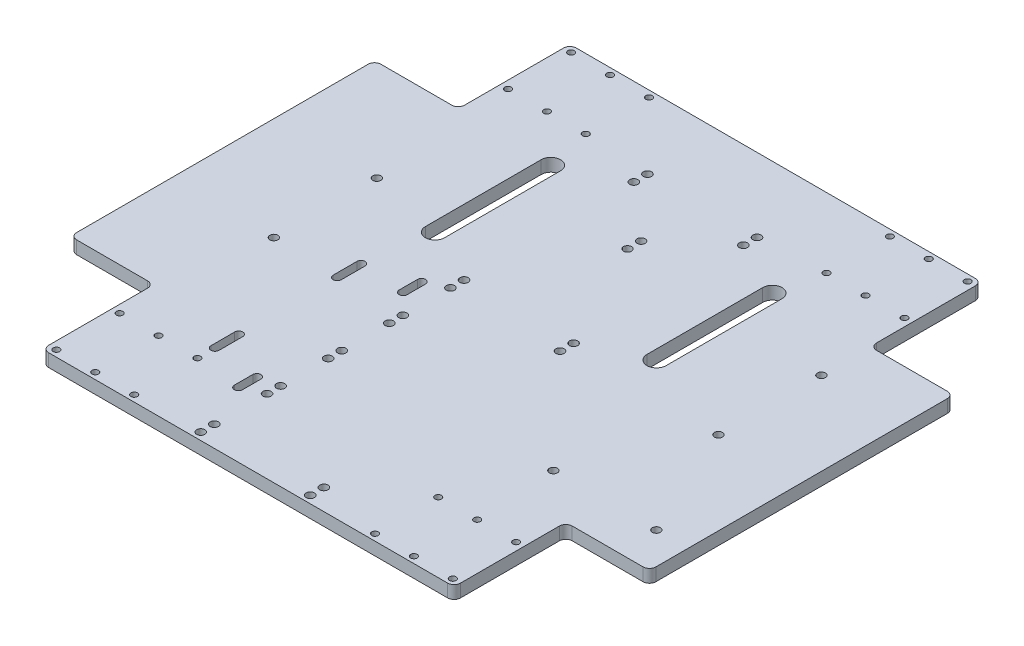
SolidWorks part; units mm, degrees
ref_plane "Front Plane" through (0, 0, 0) normal (0, 0, 1) x (1, 0, 0)
ref_plane "Top Plane" through (0, 0, 0) normal (0, 1, 0) x (1, 0, 0)
ref_plane "Right Plane" through (0, 0, 0) normal (1, 0, 0) x (0, 0, -1)
sketch "Sketch1" plane through (0, 0, 0) normal (0, 1, 0) x (1, 0, 0)
  line L1 (-101.6, 130.175) -> (101.6, 130.175)
  line L2 (-101.6, 130.175) -> (-101.6, -130.175)
  line L3 (-101.6, -130.175) -> (101.6, -130.175)
  line L4 (101.6, 130.175) -> (101.6, -130.175)
  line L5 (-101.6, 130.175) -> (101.6, -130.175) construction
  line L6 (-101.6, -130.175) -> (101.6, 130.175) construction
  point P0 (0, 0)
  dimension "D1" = 260.35
  dimension "D2" = 203.2
extrude "Boss-Extrude1" add sketch "Sketch1" against normal blind 6.35
sketch "Sketch2" plane through (0, 0, 0) normal (0, 1, 0) x (1, 0, 0)
  line L0 (0, 130.175) -> (0, -130.175) construction
  line L1 (101.6, 0) -> (-101.6, 0) construction
  line L2 (-27.0205, -117.2972) -> (27.0205, -117.2972)
  line L3 (-27.0205, -117.2972) -> (-27.0205, -124.0028)
  line L4 (101.6, -130.175) -> (101.6, 130.175)
  line L5 (101.6, 130.175) -> (-101.6, 130.175)
  line L6 (-101.6, 130.175) -> (-101.6, -130.175)
  line L7 (-101.6, -130.175) -> (101.6, -130.175)
  line L8 (101.6, -130.175) -> (101.6, 130.175)
  line L9 (101.6, 130.175) -> (-101.6, 130.175)
  line L10 (-101.6, 130.175) -> (-101.6, -130.175)
  line L11 (-101.6, -130.175) -> (101.6, -130.175)
  line L12 (-27.0205, -124.0028) -> (27.0205, -124.0028)
  line L13 (27.0205, -117.2972) -> (27.0205, -124.0028)
  line L14 (-27.0205, -117.2972) -> (27.0205, -124.0028) construction
  line L15 (-27.0205, -124.0028) -> (27.0205, -117.2972) construction
  line L16 (-27.0205, -87.1347) -> (-27.0205, -93.8403)
  line L17 (-27.0205, -87.1347) -> (27.0205, -87.1347)
  line L18 (27.0205, -87.1347) -> (27.0205, -93.8403)
  line L19 (-27.0205, -93.8403) -> (27.0205, -93.8403)
  line L20 (-27.0205, -56.9722) -> (-27.0205, -63.6778)
  line L21 (-27.0205, -56.9722) -> (27.0205, -56.9722)
  line L22 (27.0205, -56.9722) -> (27.0205, -63.6778)
  line L23 (-27.0205, -63.6778) -> (27.0205, -63.6778)
  line L24 (-27.0205, -26.8097) -> (-27.0205, -33.5153)
  line L25 (-27.0205, -26.8097) -> (27.0205, -26.8097)
  line L26 (27.0205, -26.8097) -> (27.0205, -33.5153)
  line L27 (-27.0205, -33.5153) -> (27.0205, -33.5153)
  line L28 (-27.0205, 3.3528) -> (-27.0205, -3.3528)
  line L29 (-27.0205, 3.3528) -> (27.0205, 3.3528)
  line L30 (27.0205, 3.3528) -> (27.0205, -3.3528)
  line L31 (-27.0205, -3.3528) -> (27.0205, -3.3528)
  line L32 (-27.0205, 33.5153) -> (-27.0205, 26.8097)
  line L33 (-27.0205, 33.5153) -> (27.0205, 33.5153)
  line L34 (27.0205, 33.5153) -> (27.0205, 26.8097)
  line L35 (-27.0205, 26.8097) -> (27.0205, 26.8097)
  line L36 (-27.0205, 63.6778) -> (-27.0205, 56.9722)
  line L37 (-27.0205, 63.6778) -> (27.0205, 63.6778)
  line L38 (27.0205, 63.6778) -> (27.0205, 56.9722)
  line L39 (-27.0205, 56.9722) -> (27.0205, 56.9722)
  line L40 (-27.0205, 93.8403) -> (-27.0205, 87.1347)
  line L41 (-27.0205, 93.8403) -> (27.0205, 93.8403)
  line L42 (27.0205, 93.8403) -> (27.0205, 87.1347)
  line L43 (-27.0205, 87.1347) -> (27.0205, 87.1347)
  line L44 (-27.0205, 124.0028) -> (-27.0205, 117.2972)
  line L45 (-27.0205, 124.0028) -> (27.0205, 124.0028)
  line L46 (27.0205, 124.0028) -> (27.0205, 117.2972)
  line L47 (-27.0205, 117.2972) -> (27.0205, 117.2972)
  line L48 (-27.0205, -124.0028) -> (-27.0205, -126.5428)
  line L49 (-27.0205, -117.2972) -> (-27.0205, -119.8372)
  circle A0 centre (-27.0205, -117.2972) radius 2.032
  circle A1 centre (-27.0205, -124.0028) radius 2.032
  circle A2 centre (27.0205, -124.0028) radius 2.032
  circle A3 centre (27.0205, -117.2972) radius 2.032
  circle A4 centre (-27.0205, -87.1347) radius 2.032
  circle A5 centre (-27.0205, -93.8403) radius 2.032
  circle A6 centre (27.0205, -87.1347) radius 2.032
  circle A7 centre (27.0205, -93.8403) radius 2.032
  circle A8 centre (-27.0205, -56.9722) radius 2.032
  circle A9 centre (-27.0205, -63.6778) radius 2.032
  circle A10 centre (27.0205, -56.9722) radius 2.032
  circle A11 centre (27.0205, -63.6778) radius 2.032
  circle A12 centre (-27.0205, -26.8097) radius 2.032
  circle A13 centre (-27.0205, -33.5153) radius 2.032
  circle A14 centre (27.0205, -26.8097) radius 2.032
  circle A15 centre (27.0205, -33.5153) radius 2.032
  circle A16 centre (-27.0205, 3.3528) radius 2.032
  circle A17 centre (-27.0205, -3.3528) radius 2.032
  circle A18 centre (27.0205, 3.3528) radius 2.032
  circle A19 centre (27.0205, -3.3528) radius 2.032
  circle A20 centre (-27.0205, 33.5153) radius 2.032
  circle A21 centre (-27.0205, 26.8097) radius 2.032
  circle A22 centre (27.0205, 33.5153) radius 2.032
  circle A23 centre (27.0205, 26.8097) radius 2.032
  circle A24 centre (-27.0205, 63.6778) radius 2.032
  circle A25 centre (-27.0205, 56.9722) radius 2.032
  circle A26 centre (27.0205, 63.6778) radius 2.032
  circle A27 centre (27.0205, 56.9722) radius 2.032
  circle A28 centre (-27.0205, 93.8403) radius 2.032
  circle A29 centre (-27.0205, 87.1347) radius 2.032
  circle A30 centre (27.0205, 93.8403) radius 2.032
  circle A31 centre (27.0205, 87.1347) radius 2.032
  circle A32 centre (-27.0205, 124.0028) radius 2.032
  circle A33 centre (-27.0205, 117.2972) radius 2.032
  circle A34 centre (27.0205, 124.0028) radius 2.032
  circle A35 centre (27.0205, 117.2972) radius 2.032
  circle A36 centre (-27.0205, -119.8372) radius 2.032
  circle A37 centre (-27.0205, -126.5428) radius 2.032
  circle A38 centre (27.0205, -126.5428) radius 2.032
  circle A39 centre (27.0205, -119.8372) radius 2.032
  circle A40 centre (0, 63.6778) radius 1.9939
  circle A41 centre (0, 56.9722) radius 1.9939
  point P6 (0, -120.65)
  dimension "D5" = 4.064
  dimension "D6" = 4.064
  dimension "D7" = 4.064
  dimension "D8" = 4.064
  dimension "D13" = 4.064
  dimension "D14" = 4.064
  dimension "D15" = 3.9878
  dimension "D16" = 3.9878
  dimension "D2" = 6.7056
  dimension "D3" = 54.041
  dimension "D4" = 6.1722
  dimension "D10" = 30.1625
  dimension "D11" = 2.54
  dimension "D12" = 2.54
  dimension "D1" = 0
  dimension "D9" = 9
extrude "Cut-Extrude1" cut sketch "Sketch2" against normal through all contours L43 A29 L40 | L40 A29 L43 | L41 A30 L42 | L28 A16 L29 | L29 A16 L28 | L31 A17 L28 | L28 A17 L31 | L29 A18 L30 | L30 A18 L29 | L30 A19 L31 | L31 A19 L30 | L42 A30 L41 | L43 A31 L42 | L42 A31 L43 | L41 A28 L40 | L40 A28 L41 | L25 A12 L24 | L24 A12 L25 | L27 A13 L24 | L24 A13 L27 | L21 A8 L20 | L20 A8 L21 | L20 A9 L23 | L23 A9 L20 | L17 A4 L16 | L16 A4 L17 | L16 A5 L19 | L19 A5 L16 | A36 | A37 | A39 | A38 | A40 | A41 region at (-26.1581, 0, 87.9971) region at (-27.308, 0, 86.8472) region at (-26.1581, 0, 92.9779) region at (-27.308, 0, 94.1278) region at (-26.1581, 0, 57.8346) region at (-27.308, 0, 56.6847) region at (-26.1581, 0, 62.8154) region at (-27.308, 0, 63.9653) region at (-26.1581, 0, 27.6721) region at (-27.308, 0, 26.5222) region at (-26.1581, 0, 32.6529) region at (-27.308, 0, 33.8028) region at (-26.1581, 0, -2.4904) region at (-27.308, 0, -3.6403) region at (-26.1581, 0, 2.4904) region at (-27.308, 0, 3.6403) region at (27.308, 0, -3.6403) region at (26.1581, 0, -2.4904) region at (26.1581, 0, 2.4904) region at (27.308, 0, 3.6403) region at (-26.1581, 0, -92.9779) region at (-27.308, 0, -94.1278) region at (-26.1581, 0, -87.9971) region at (-27.308, 0, -86.8472) region at (27.308, 0, -94.1278) region at (26.1581, 0, -92.9779) region at (26.1581, 0, -87.9971) region at (27.308, 0, -86.8472)
sketch "Sketch3" plane through (0, 0, 0) normal (0, 1, 0) x (1, 0, 0)
  line L0 (101.6, 130.175) -> (-101.6, 130.175) construction
  line L1 (101.6, -130.175) -> (101.6, 130.175) construction
  line L2 (-101.6, 130.175) -> (-101.6, -130.175) construction
  line L3 (-101.6, -130.175) -> (101.6, -130.175) construction
  line L4 (101.6, 130.175) -> (-101.6, 130.175)
  line L5 (101.6, -130.175) -> (101.6, 130.175)
  line L6 (-101.6, 130.175) -> (-101.6, -130.175)
  line L7 (-101.6, -130.175) -> (101.6, -130.175)
  line L8 (0, -130.175) -> (0, 130.175) construction
  line L9 (-101.6, 0) -> (101.6, 0) construction
  circle A10 centre (-85.0055, -95.8) radius 1.6
  circle A11 centre (-85.0055, -127) radius 1.6
  circle A12 centre (-78.6055, -95.8) radius 1.6
  circle A13 centre (-78.6055, -127) radius 1.6
  circle A14 centre (-72.2055, -95.8) radius 1.6
  circle A15 centre (-72.2055, -127) radius 1.6
  circle A16 centre (-65.8055, -95.8) radius 1.6
  circle A17 centre (-59.4055, -95.8) radius 1.6
  circle A18 centre (-65.8055, -127) radius 1.6
  circle A19 centre (-59.4055, -127) radius 1.6
  circle A22 centre (85.0055, -127) radius 1.6
  circle A23 centre (78.6055, -127) radius 1.6
  circle A24 centre (72.2055, -127) radius 1.6
  circle A25 centre (65.8055, -127) radius 1.6
  circle A26 centre (59.4055, -127) radius 1.6
  circle A27 centre (59.4055, -95.8) radius 1.6
  circle A28 centre (65.8055, -95.8) radius 1.6
  circle A29 centre (72.2055, -95.8) radius 1.6
  circle A30 centre (78.6055, -95.8) radius 1.6
  circle A31 centre (85.0055, -95.8) radius 1.6
  circle A32 centre (85.0055, 127) radius 1.6
  circle A33 centre (78.6055, 127) radius 1.6
  circle A34 centre (72.2055, 127) radius 1.6
  circle A35 centre (65.8055, 127) radius 1.6
  circle A36 centre (59.4055, 127) radius 1.6
  circle A37 centre (85.0055, 95.8) radius 1.6
  circle A38 centre (78.6055, 95.8) radius 1.6
  circle A39 centre (72.2055, 95.8) radius 1.6
  circle A40 centre (65.8055, 95.8) radius 1.6
  circle A41 centre (59.4055, 95.8) radius 1.6
  circle A42 centre (-59.4055, 127) radius 1.6
  circle A43 centre (-65.8055, 127) radius 1.6
  circle A44 centre (-72.2055, 127) radius 1.6
  circle A45 centre (-78.6055, 127) radius 1.6
  circle A46 centre (-85.0055, 127) radius 1.6
  circle A47 centre (-59.4055, 95.8) radius 1.6
  circle A48 centre (-65.8055, 95.8) radius 1.6
  circle A49 centre (-72.2055, 95.8) radius 1.6
  circle A50 centre (-78.6055, 95.8) radius 1.6
  circle A51 centre (-85.0055, 95.8) radius 1.6
  circle A52 centre (-91.4063, -127) radius 1.6
  circle A53 centre (-91.4063, -95.8) radius 1.6
  circle A54 centre (-97.8071, -127) radius 1.6
  circle A55 centre (-97.8071, -95.8) radius 1.6
  circle A56 centre (97.8071, -127) radius 1.6
  circle A57 centre (91.4063, -127) radius 1.6
  circle A58 centre (97.8071, -95.8) radius 1.6
  circle A59 centre (91.4063, -95.8) radius 1.6
  circle A60 centre (97.8071, 95.8) radius 1.6
  circle A61 centre (97.8071, 127) radius 1.6
  circle A62 centre (91.4063, 127) radius 1.6
  circle A63 centre (91.4063, 95.8) radius 1.6
  circle A64 centre (-97.8071, 127) radius 1.6
  circle A65 centre (-91.4063, 127) radius 1.6
  circle A66 centre (-97.8071, 95.8) radius 1.6
  circle A67 centre (-91.4063, 95.8) radius 1.6
  circle A68 centre (-27.0205, -126.5428) radius 2.032 construction
  point P9 (85.0055, -95.8)
  point P10 (78.6055, -95.8)
  point P11 (72.2055, -95.8)
  point P12 (65.8055, -95.8)
  point P13 (59.4055, -95.8)
  point P14 (78.6055, -127)
  point P15 (72.2055, -127)
  point P18 (85.0055, -127)
  point P19 (59.4055, -127)
  point P62 (85.0055, 127)
  point P65 (78.6055, 127)
  point P68 (72.2055, 127)
  point P73 (59.4055, 127)
  point P76 (85.0055, 95.8)
  point P79 (78.6055, 95.8)
  point P82 (72.2055, 95.8)
  point P85 (65.8055, 95.8)
  point P88 (59.4055, 95.8)
  dimension "D3" = 31.2
  dimension "D5" = 31.2
  dimension "D7" = 3
  dimension "D8" = 6.4008
  dimension "D9" = 32.385
  dimension "D24" = 3.2
  dimension "D25" = 3.2
  dimension "D26" = 3.2
  dimension "D27" = 3.2
  dimension "D28" = 3.2
  dimension "D31" = 3.2
  dimension "D32" = 3.2
  dimension "D33" = 3.2
  dimension "D34" = 3.2
  dimension "D35" = 3.2
  dimension "D4" = 31.2
  dimension "D6" = 31.2
  dimension "D10" = 6.4
  dimension "D11" = 6.4
  dimension "D12" = 6.4
  dimension "D13" = 6.4
  dimension "D16" = 6.4
  dimension "D17" = 6.4
  dimension "D18" = 6.4
  dimension "D19" = 6.4
  dimension "D22" = 31.2
  dimension "D37" = 3.175
extrude "Cut-Extrude2" cut sketch "Sketch3" against normal up to surface (6.35 mm away) contours A17 | A12 | A19 | A13 | A26 | A27 | A30 | A23 | A38 | A36 | A33 | A41 | A47 | A50 | A42 | A45 | A55 | A54 | A56 | A58 | A60 | A61 | A64 | A66 | A41 region at (-78.6055, 0, 95.8) region at (-78.6055, 0, 127) region at (-59.4055, 0, 95.8) region at (-59.4055, 0, 127) region at (78.6055, 0, 127) region at (59.4055, 0, 127) region at (59.4055, 0, 95.8) region at (78.6055, 0, 95.8) region at (78.6055, 0, -127) region at (59.4055, 0, -127) region at (78.6055, 0, -95.8) region at (59.4055, 0, -95.8) region at (-59.4055, 0, -127) region at (-78.6055, 0, -127) region at (-59.4055, 0, -95.8) region at (-78.6055, 0, -95.8) region at (-97.8071, 0, 127) region at (-97.8071, 0, 95.8) region at (97.8071, 0, 127) region at (97.8071, 0, 95.8) region at (97.8071, 0, -95.8) region at (97.8071, 0, -127) region at (-97.8071, 0, -127) region at (-97.8071, 0, -95.8) up to face at (-27.0205, -6.35, 28.8417)
sketch "Sketch4" plane through (0, 0, 0) normal (0, 1, 0) x (1, 0, 0)
  line L0 (-27.0205, -87.1347) -> (-27.0205, -63.6778)
  line L1 (-27.0205, -75.4063) -> (-59.4055, -75.4063)
  line L2 (-59.4055, -95.8) -> (-59.4055, -75.4063)
  line L3 (-27.0205, -87.1347) -> (-59.4055, -87.1347)
  line L4 (-61.3994, -75.4063) -> (-61.3994, -87.1347)
  line L5 (-57.4116, -75.4063) -> (-57.4116, -87.1347)
  line L6 (-27.0205, -87.1347) -> (-27.0205, -93.8403)
  line L7 (-27.0205, -90.4875) -> (-36.7792, -90.4875)
  line L8 (-36.7792, -90.4875) -> (-36.7792, -9.217)
  line L9 (-27.0205, -3.3528) -> (-27.0205, -26.8097)
  line L10 (-27.0205, -15.0813) -> (-36.7792, -15.0813)
  line L11 (-27.0205, -3.3528) -> (-36.7792, -3.3528)
  line L12 (-36.7792, -3.3528) -> (-36.7792, -15.0813)
  line L13 (-38.7731, -89.1286) -> (-38.7731, -91.8464)
  line L14 (-34.7853, -89.1286) -> (-34.7853, -91.8464)
  line L15 (-34.7853, -7.8581) -> (-34.7853, -10.5759)
  line L16 (-38.7731, -7.8581) -> (-38.7731, -10.5759)
  line L17 (-27.0205, -26.8097) -> (-59.4055, -26.8097)
  line L18 (-36.7792, -15.0813) -> (-59.4055, -15.0813)
  line L19 (-61.3994, -26.8097) -> (-61.3994, -15.0813)
  line L20 (-57.4116, -15.0813) -> (-57.4116, -26.8097)
  line L21 (-38.7731, -91.8464) -> (-38.7731, -98.1964)
  line L22 (-34.7853, -91.8464) -> (-34.7853, -98.1964)
  line L23 (-38.7731, -10.5759) -> (-38.7731, -16.9259)
  line L24 (-34.7853, -10.5759) -> (-34.7853, -16.9259)
  circle A0 centre (-27.0205, -93.8403) radius 2.032 construction
  circle A1 centre (-27.0205, -63.6778) radius 2.032 construction
  circle A2 centre (-27.0205, -87.1347) radius 2.032 construction
  circle A3 centre (-59.4055, -127) radius 1.6 construction
  circle A4 centre (-59.4055, -95.8) radius 1.6 construction
  circle A5 centre (-27.0205, -93.8403) radius 2.032
  circle A6 centre (-27.0205, -63.6778) radius 2.032
  circle A7 centre (-27.0205, -87.1347) radius 2.032
  circle A8 centre (-59.4055, -127) radius 1.6
  circle A9 centre (-59.4055, -95.8) radius 1.6
  circle A10 centre (-59.4055, -87.1347) radius 1.9939
  circle A11 centre (-59.4055, -75.4063) radius 1.9939
  circle A12 centre (-36.7792, -9.217) radius 1.9939
  circle A13 centre (-36.7792, -90.4875) radius 1.9939
  circle A16 centre (-27.0205, -3.3528) radius 2.032 construction
  circle A17 centre (-27.0205, -26.8097) radius 2.032 construction
  circle A18 centre (-27.0205, -3.3528) radius 2.032
  circle A19 centre (-27.0205, -26.8097) radius 2.032
  circle A20 centre (-36.7792, -89.1286) radius 1.9939
  circle A21 centre (-36.7792, -91.8464) radius 1.9939
  circle A22 centre (-36.7792, -7.8581) radius 1.9939
  circle A23 centre (-36.7792, -10.5759) radius 1.9939
  circle A24 centre (-59.4055, -15.0813) radius 1.9939
  circle A25 centre (-59.4055, -26.8097) radius 1.9939
  circle A26 centre (-36.7792, -98.1964) radius 1.9939
  circle A27 centre (-36.7792, -16.9259) radius 1.9939
  point P48 (-34.7853, -9.217)
  dimension "D1" = 3.9878
  dimension "D2" = 3.9878
  dimension "D6" = 3.9878
  dimension "D7" = 3.9878
  dimension "D8" = 3.9878
  dimension "D10" = 3.9878
  dimension "D11" = 3.9878
  dimension "D12" = 3.9878
  dimension "D15" = 6.35
  dimension "D3" = 9.7587
  dimension "D4" = 9.7587
  dimension "D5" = 81.2705
  dimension "D9" = 2.7178
  dimension "D13" = 6.35
  dimension "D14" = 6.35
  dimension "D16" = 6.35
extrude "Cut-Extrude3" cut sketch "Sketch4" against normal through all contours L1 A11 L2 | L2 A11 L1 | A11 L4 A10 L2 | L2 A10 L3 | L3 A10 L2 | A11 L2 A10 L5 | L2 A10 | A25 | A25 L20 A24 L19 | A24 | A12 A22 L12 | L12 A22 A12 | A23 L12 A12 A22 | A23 A22 A12 L12 | A22 L16 A12 | A22 A12 L15 | A23 A22 A12 | L12 A23 A22 L8 | A22 A23 L12 L8 | A23 A12 A22 | A23 A12 L16 | A22 A23 A12 L12 | A12 A23 A22 L12 | A23 L15 A12 | L12 A23 A12 | A12 A23 L12 | A13 A20 L8 | L8 A20 A13 | A20 L13 A13 | A20 A13 L14 | L8 A21 A20 A13 | A20 A21 L8 A13 | A13 A21 A20 | A21 A20 L7 L8 | A21 L8 L7 | A20 L7 A13 | L7 A21 A13 | A13 A21 L14 | L13 A21 A13 | A21 A13 A20 | A21 A13 | A26 L22 A21 L21 | A26 | A27 L10 L24 A23 L12 | A27 L12 A23 L23 L18 | A27 L18 L23 | A27 L24 L10 | L8 A27 L10 | L18 A27 L8 | L8 A27 L18 | L10 A27 L8 | A27 region at (-35.8016, 0, 88.2106) region at (-37.7568, 0, 88.2106) region at (-58.5593, 0, 87.9809) region at (-58.3537, 0, 81.2705) region at (-58.5593, 0, 86.2885) region at (-35.9259, 0, 89.4309) region at (-37.6325, 0, 89.4309) region at (-34.8209, 0, 89.8081) region at (-38.7375, 0, 89.8081) region at (-34.9781, 0, 90.7103) region at (-34.9781, 0, 90.2647) region at (-34.8209, 0, 91.1669) region at (-58.5593, 0, 76.2525) region at (-59.6876, 0, 75.1242) region at (-60.2518, 0, 87.1347) region at (-60.4574, 0, 81.2705) region at (-36.2182, 0, 90.2297) region at (-36.9662, 0, 90.5734) region at (-38.5803, 0, 90.4875) region at (-38.7375, 0, 91.1669) region at (-36.7792, 0, 91.5441) region at (-36.7792, 0, 95.0214) region at (-36.7792, 0, 92.7644) region at (-37.6323, 0, 16.9493) region at (-35.9261, 0, 16.9493) region at (-59.4055, 0, 20.9455) region at (-59.4055, 0, 28.7472) region at (-36.7792, 0, 98.1964) region at (-37.0645, 0, 15.0214) region at (-36.4939, 0, 15.0214) region at (-38.4358, 0, 15.5093) region at (-35.1226, 0, 15.5093) region at (-59.4055, 0, 17.0188) region at (-37.8668, 0, 13.559) region at (-35.6916, 0, 13.559) region at (-37.7568, 0, 11.494) region at (-35.8016, 0, 11.494) region at (-38.7375, 0, 9.8965) region at (-34.8209, 0, 9.8965) region at (-37.6325, 0, 10.2736) region at (-35.9259, 0, 10.2736) region at (-38.7375, 0, 8.5376) region at (-38.5803, 0, 9.217) region at (-34.8209, 0, 8.5376) region at (-34.9781, 0, 9.217) region at (-37.3402, 0, 9.217) region at (-36.2182, 0, 9.217) region at (-37.7568, 0, 6.9401) region at (-37.6325, 0, 8.1604) region at (-35.8016, 0, 6.9401) region at (-35.9259, 0, 8.1604)
sketch "Sketch5" plane through (0, 0, 0) normal (0, 1, 0) x (1, 0, 0)
  line L0 (-101.6, -130.175) -> (101.6, 130.175) construction
  line L1 (-101.6, 130.175) -> (101.6, -130.175) construction
  line L2 (-101.6, -130.175) -> (101.6, -130.175) construction
  line L3 (101.6, 130.175) -> (101.6, -130.175) construction
  line L4 (-101.6, 130.175) -> (101.6, 130.175) construction
  line L5 (-101.6, 130.175) -> (-101.6, -130.175) construction
  line L6 (-101.6, -130.175) -> (101.6, 130.175) construction
  line L7 (-101.6, 130.175) -> (101.6, -130.175) construction
  line L8 (-101.6, -130.175) -> (101.6, -130.175)
  line L9 (101.6, 130.175) -> (101.6, -130.175)
  line L10 (-101.6, 130.175) -> (101.6, 130.175)
  line L11 (-101.6, 130.175) -> (-101.6, -130.175)
  line L12 (-97.8071, -127) -> (-97.8071, -95.8) construction
  line L13 (-97.8071, -111.4) -> (-110.5071, -111.4)
  line L14 (-110.5071, -81.4001) -> (-110.5071, -141.3999)
  line L15 (-101.6, 0) -> (101.6, 0) construction
  line L16 (0, 130.175) -> (0, -130.175) construction
  line L17 (-110.5071, -81.4001) -> (-101.6, -81.4001)
  line L18 (-142.875, -75.0501) -> (142.875, -75.0501)
  line L19 (-142.875, 75.0501) -> (142.875, 75.0501)
  line L20 (-142.875, 75.0501) -> (-142.875, -75.0501)
  line L21 (142.875, 75.0501) -> (142.875, -75.0501)
  circle A0 centre (-97.8071, -127) radius 1.6 construction
  circle A1 centre (-97.8071, -95.8) radius 1.6 construction
  circle A2 centre (-97.8071, -127) radius 1.6
  circle A3 centre (-97.8071, -95.8) radius 1.6
  point P14 (-110.5071, -111.4)
  point P22 (0, -75.0501)
  dimension "D1" = 12.7
  dimension "D2" = 59.9999
  dimension "D3" = 285.75
  dimension "D4" = 6.35
extrude "Boss-Extrude2" add sketch "Sketch5" against normal blind 6.35 contours L21 L19 L9 L18 | L19 L20 L18 L11 region at (122.2375, 0, 0) region at (-122.2375, 0, 0)
fillet "Fillet1" radius 3.175 12 edges at (-101.6, -3.175, -130.175) (-101.6, -3.175, -75.0501) (-142.875, -3.175, -75.0501) (-142.875, -3.175, 75.0501) (-101.6, -3.175, 75.0501) (-101.6, -3.175, 130.175) (101.6, -3.175, 130.175) (101.6, -3.175, 75.0501) (142.875, -3.175, 75.0501) (142.875, -3.175, -75.0501) (101.6, -3.175, -75.0501) (101.6, -3.175, -130.175)
sketch "Sketch6" plane through (0, 0, 0) normal (0, 1, 0) x (1, 0, 0)
  line L0 (-57.4116, -15.0813) -> (-57.4116, -26.8097) construction
  line L1 (-61.3994, -26.8097) -> (-61.3994, -15.0813) construction
  line L2 (-57.4116, -15.0813) -> (-57.4116, -26.8097)
  line L3 (-61.3994, -26.8097) -> (-61.3994, -15.0813)
  line L4 (-61.3994, -15.0813) -> (-142.875, -15.0813) construction
  line L5 (-92.075, 130.175) -> (-92.075, -130.175) construction
  line L6 (29.0525, -3.3528) -> (60.8025, -3.3528) construction
  line L7 (60.8025, 130.175) -> (60.8025, -130.175) construction
  line L8 (-57.4116, -75.4063) -> (-57.4116, -87.1347) construction
  line L9 (-57.4116, -75.4063) -> (-57.4116, -87.1347)
  line L10 (-61.3994, -75.4063) -> (-61.3994, -87.1347) construction
  line L11 (-61.3994, -75.4063) -> (-61.3994, -87.1347)
  line L12 (98.425, 130.175) -> (-98.425, 130.175)
  line L13 (-101.6, 127) -> (-101.6, 78.2251)
  line L14 (-104.775, 75.0501) -> (-139.7, 75.0501)
  line L15 (-142.875, 71.8751) -> (-142.875, -71.8751)
  line L16 (-139.7, -75.0501) -> (-104.775, -75.0501)
  line L17 (-101.6, -78.2251) -> (-101.6, -127)
  line L18 (-98.425, -130.175) -> (98.425, -130.175)
  line L19 (101.6, -127) -> (101.6, -78.2251)
  line L20 (104.775, -75.0501) -> (139.7, -75.0501)
  line L21 (142.875, -71.8751) -> (142.875, 71.8751)
  line L22 (139.7, 75.0501) -> (104.775, 75.0501)
  line L23 (101.6, 78.2251) -> (101.6, 127)
  line L24 (98.425, 130.175) -> (-98.425, 130.175)
  line L25 (-101.6, 127) -> (-101.6, 78.2251)
  line L26 (-104.775, 75.0501) -> (-139.7, 75.0501)
  line L27 (-142.875, 71.8751) -> (-142.875, -71.8751)
  line L28 (-139.7, -75.0501) -> (-104.775, -75.0501)
  line L29 (-101.6, -78.2251) -> (-101.6, -127)
  line L30 (-98.425, -130.175) -> (98.425, -130.175)
  line L31 (101.6, -127) -> (101.6, -78.2251)
  line L32 (104.775, -75.0501) -> (139.7, -75.0501)
  line L33 (142.875, -71.8751) -> (142.875, 71.8751)
  line L34 (139.7, 75.0501) -> (104.775, 75.0501)
  line L35 (101.6, 78.2251) -> (101.6, 127)
  line L36 (-92.075, 25.4) -> (-92.075, -25.4)
  line L37 (60.8025, 0) -> (142.875, 0) construction
  line L38 (101.8388, 77.0171) -> (101.8388, -77.0171) construction
  line L39 (76.4388, -56.0001) -> (127.2388, -56.0001)
  line L40 (101.8388, 50.8) -> (101.8388, 0)
  arc A0 (-61.3994, -26.8097) -> (-57.4116, -26.8097) centre (-59.4055, -26.8097) ccw construction
  arc A1 (-57.4116, -15.0813) -> (-61.3994, -15.0813) centre (-59.4055, -15.0813) ccw construction
  arc A2 (-61.3994, -26.8097) -> (-57.4116, -26.8097) centre (-59.4055, -26.8097) ccw
  arc A3 (-57.4116, -15.0813) -> (-61.3994, -15.0813) centre (-59.4055, -15.0813) ccw
  circle A4 centre (27.0205, -3.3528) radius 2.032 construction
  circle A5 centre (27.0205, -3.3528) radius 2.032
  circle A6 centre (-27.0205, -87.1347) radius 2.032 construction
  circle A7 centre (-27.0205, -87.1347) radius 2.032
  arc A8 (-57.4116, -75.4063) -> (-61.3994, -75.4063) centre (-59.4055, -75.4063) ccw construction
  arc A9 (-61.3994, -87.1347) -> (-57.4116, -87.1347) centre (-59.4055, -87.1347) ccw construction
  arc A10 (-57.4116, -75.4063) -> (-61.3994, -75.4063) centre (-59.4055, -75.4063) ccw
  arc A11 (-61.3994, -87.1347) -> (-57.4116, -87.1347) centre (-59.4055, -87.1347) ccw
  arc A12 (-98.425, 130.175) -> (-101.6, 127) centre (-98.425, 127) ccw
  arc A13 (-104.775, 75.0501) -> (-101.6, 78.2251) centre (-104.775, 78.2251) ccw
  arc A14 (-139.7, 75.0501) -> (-142.875, 71.8751) centre (-139.7, 71.8751) ccw
  arc A15 (-142.875, -71.8751) -> (-139.7, -75.0501) centre (-139.7, -71.8751) ccw
  arc A16 (-101.6, -78.2251) -> (-104.775, -75.0501) centre (-104.775, -78.2251) ccw
  arc A17 (-101.6, -127) -> (-98.425, -130.175) centre (-98.425, -127) ccw
  arc A18 (98.425, -130.175) -> (101.6, -127) centre (98.425, -127) ccw
  arc A19 (104.775, -75.0501) -> (101.6, -78.2251) centre (104.775, -78.2251) ccw
  arc A20 (139.7, -75.0501) -> (142.875, -71.8751) centre (139.7, -71.8751) ccw
  arc A21 (142.875, 71.8751) -> (139.7, 75.0501) centre (139.7, 71.8751) ccw
  arc A22 (101.6, 78.2251) -> (104.775, 75.0501) centre (104.775, 78.2251) ccw
  arc A23 (101.6, 127) -> (98.425, 130.175) centre (98.425, 127) ccw
  arc A24 (-98.425, 130.175) -> (-101.6, 127) centre (-98.425, 127) ccw
  arc A25 (-104.775, 75.0501) -> (-101.6, 78.2251) centre (-104.775, 78.2251) ccw
  arc A26 (-139.7, 75.0501) -> (-142.875, 71.8751) centre (-139.7, 71.8751) ccw
  arc A27 (-142.875, -71.8751) -> (-139.7, -75.0501) centre (-139.7, -71.8751) ccw
  arc A28 (-101.6, -78.2251) -> (-104.775, -75.0501) centre (-104.775, -78.2251) ccw
  arc A29 (-101.6, -127) -> (-98.425, -130.175) centre (-98.425, -127) ccw
  arc A30 (98.425, -130.175) -> (101.6, -127) centre (98.425, -127) ccw
  arc A31 (104.775, -75.0501) -> (101.6, -78.2251) centre (104.775, -78.2251) ccw
  arc A32 (139.7, -75.0501) -> (142.875, -71.8751) centre (139.7, -71.8751) ccw
  arc A33 (142.875, 71.8751) -> (139.7, 75.0501) centre (139.7, 71.8751) ccw
  arc A34 (101.6, 78.2251) -> (104.775, 75.0501) centre (104.775, 78.2251) ccw
  arc A35 (101.6, 127) -> (98.425, 130.175) centre (98.425, 127) ccw
  circle A36 centre (-92.075, 25.4) radius 1.9939
  circle A37 centre (-92.075, -25.4) radius 1.9939
  circle A38 centre (76.4388, -56.0001) radius 1.9939
  circle A39 centre (127.2388, -56.0001) radius 1.9939
  circle A40 centre (101.8388, 0) radius 1.9939
  circle A41 centre (101.8388, 50.8) radius 1.9939
  point P61 (-92.075, 0)
  point P63 (-92.075, 0)
  point P69 (101.8388, 0)
  point P72 (101.8388, 0)
  point P73 (101.8388, -56.0001)
  dimension "D5" = 3.9878
  dimension "D6" = 3.9878
  dimension "D11" = 3.9878
  dimension "D12" = 3.9878
  dimension "D14" = 3.9878
  dimension "D15" = 3.9878
  dimension "D2" = 31.75
  dimension "D3" = 32.385
  dimension "D4" = 50.8
  dimension "D7" = 81.4756
  dimension "D8" = 50.8
  dimension "D9" = 50.8
  dimension "D10" = 19.05
  dimension "D13" = 50.8
  dimension "D1" = 0
extrude "Cut-Extrude4" cut sketch "Sketch6" against normal blind 6.35 contours A38 | A39 | A40 | A41 | A37 | A36 region at (-90.705, 0, 24.03) region at (-93.445, 0, -26.77) region at (127.2388, 0, 54.0626) region at (74.5013, 0, 56.0001) region at (103.2088, 0, -1.37) region at (100.4687, 0, -52.17)
sketch "Sketch7" plane through (0, 0, 0) normal (0, 1, 0) x (1, 0, 0)
  line L0 (0, 130.175) -> (0, -130.175) construction
  line L1 (98.425, 130.175) -> (-98.425, 130.175) construction
  line L2 (-98.425, -130.175) -> (98.425, -130.175) construction
  line L3 (-59.4055, 130.175) -> (-59.4055, -130.175) construction
  line L4 (-27.0205, 87.1347) -> (-27.0205, 3.3528) construction
  line L5 (-27.0205, 45.2437) -> (-59.4055, 45.2437) construction
  line L6 (-54.643, 73.8187) -> (-54.643, 16.6687)
  line L7 (-59.4055, 73.8187) -> (-59.4055, 16.6687)
  line L8 (-49.8805, 73.8187) -> (-49.8805, 16.6687)
  line L9 (59.4055, 73.8187) -> (59.4055, 16.6687)
  line L10 (54.643, 73.8187) -> (54.643, 16.6687)
  line L11 (49.8805, 73.8187) -> (49.8805, 16.6687)
  line L15 (98.425, 130.175) -> (-98.425, 130.175)
  line L16 (-101.6, 127) -> (-101.6, 78.2251)
  line L17 (-104.775, 75.0501) -> (-139.7, 75.0501)
  line L18 (-142.875, 71.8751) -> (-142.875, -71.8751)
  line L19 (-139.7, -75.0501) -> (-104.775, -75.0501)
  line L20 (-101.6, -78.2251) -> (-101.6, -127)
  line L21 (-98.425, -130.175) -> (98.425, -130.175)
  line L22 (101.6, -127) -> (101.6, -78.2251)
  line L23 (104.775, -75.0501) -> (139.7, -75.0501)
  line L24 (142.875, -71.8751) -> (142.875, 71.8751)
  line L25 (139.7, 75.0501) -> (104.775, 75.0501)
  line L26 (101.6, 78.2251) -> (101.6, 127)
  line L27 (98.425, 130.175) -> (-98.425, 130.175)
  line L28 (-101.6, 127) -> (-101.6, 78.2251)
  line L29 (-104.775, 75.0501) -> (-139.7, 75.0501)
  line L30 (-142.875, 71.8751) -> (-142.875, -71.8751)
  line L31 (-139.7, -75.0501) -> (-104.775, -75.0501)
  line L32 (-101.6, -78.2251) -> (-101.6, -127)
  line L33 (-98.425, -130.175) -> (98.425, -130.175)
  line L34 (101.6, -127) -> (101.6, -78.2251)
  line L35 (104.775, -75.0501) -> (139.7, -75.0501)
  line L36 (142.875, -71.8751) -> (142.875, 71.8751)
  line L37 (139.7, 75.0501) -> (104.775, 75.0501)
  line L38 (101.6, 78.2251) -> (101.6, 127)
  circle A0 centre (-27.0205, 3.3528) radius 2.032 construction
  circle A1 centre (-27.0205, 87.1347) radius 2.032 construction
  circle A2 centre (-27.0205, 3.3528) radius 2.032
  circle A3 centre (-27.0205, 87.1347) radius 2.032
  circle A4 centre (-54.643, 73.8187) radius 4.7625
  circle A5 centre (-54.643, 16.6687) radius 4.7625
  circle A6 centre (54.643, 16.6687) radius 4.7625
  circle A7 centre (54.643, 73.8187) radius 4.7625
  arc A12 (-98.425, 130.175) -> (-101.6, 127) centre (-98.425, 127) ccw
  arc A13 (-104.775, 75.0501) -> (-101.6, 78.2251) centre (-104.775, 78.2251) ccw
  arc A14 (-139.7, 75.0501) -> (-142.875, 71.8751) centre (-139.7, 71.8751) ccw
  arc A15 (-142.875, -71.8751) -> (-139.7, -75.0501) centre (-139.7, -71.8751) ccw
  arc A16 (-101.6, -78.2251) -> (-104.775, -75.0501) centre (-104.775, -78.2251) ccw
  arc A17 (-101.6, -127) -> (-98.425, -130.175) centre (-98.425, -127) ccw
  arc A18 (98.425, -130.175) -> (101.6, -127) centre (98.425, -127) ccw
  arc A19 (104.775, -75.0501) -> (101.6, -78.2251) centre (104.775, -78.2251) ccw
  arc A20 (139.7, -75.0501) -> (142.875, -71.8751) centre (139.7, -71.8751) ccw
  arc A21 (142.875, 71.8751) -> (139.7, 75.0501) centre (139.7, 71.8751) ccw
  arc A22 (101.6, 78.2251) -> (104.775, 75.0501) centre (104.775, 78.2251) ccw
  arc A23 (101.6, 127) -> (98.425, 130.175) centre (98.425, 127) ccw
  arc A24 (-98.425, 130.175) -> (-101.6, 127) centre (-98.425, 127) ccw
  arc A25 (-104.775, 75.0501) -> (-101.6, 78.2251) centre (-104.775, 78.2251) ccw
  arc A26 (-139.7, 75.0501) -> (-142.875, 71.8751) centre (-139.7, 71.8751) ccw
  arc A27 (-142.875, -71.8751) -> (-139.7, -75.0501) centre (-139.7, -71.8751) ccw
  arc A28 (-101.6, -78.2251) -> (-104.775, -75.0501) centre (-104.775, -78.2251) ccw
  arc A29 (-101.6, -127) -> (-98.425, -130.175) centre (-98.425, -127) ccw
  arc A30 (98.425, -130.175) -> (101.6, -127) centre (98.425, -127) ccw
  arc A31 (104.775, -75.0501) -> (101.6, -78.2251) centre (104.775, -78.2251) ccw
  arc A32 (139.7, -75.0501) -> (142.875, -71.8751) centre (139.7, -71.8751) ccw
  arc A33 (142.875, 71.8751) -> (139.7, 75.0501) centre (139.7, 71.8751) ccw
  arc A34 (101.6, 78.2251) -> (104.775, 75.0501) centre (104.775, 78.2251) ccw
  arc A35 (101.6, 127) -> (98.425, 130.175) centre (98.425, 127) ccw
  point P48 (-54.643, 45.2437)
  dimension "D3" = 9.525
  dimension "D4" = 9.525
  dimension "D1" = 0
  dimension "D2" = 57.15
extrude "Cut-Extrude5" cut sketch "Sketch7" against normal through all contours A4 | A5 L8 A4 L6 | A5 L6 A4 L7 | A5 | A7 | L9 A7 L10 A6 | L10 A7 L11 A6 | A6 region at (-52.2076, 0, -45.2437) region at (-57.0785, 0, -45.2437) region at (-57.9154, 0, -70.5464) region at (-51.3707, 0, -19.9411) region at (57.9154, 0, -70.5464) region at (57.0785, 0, -45.2437) region at (54.643, 0, -12.041) region at (52.2076, 0, -45.2437)
